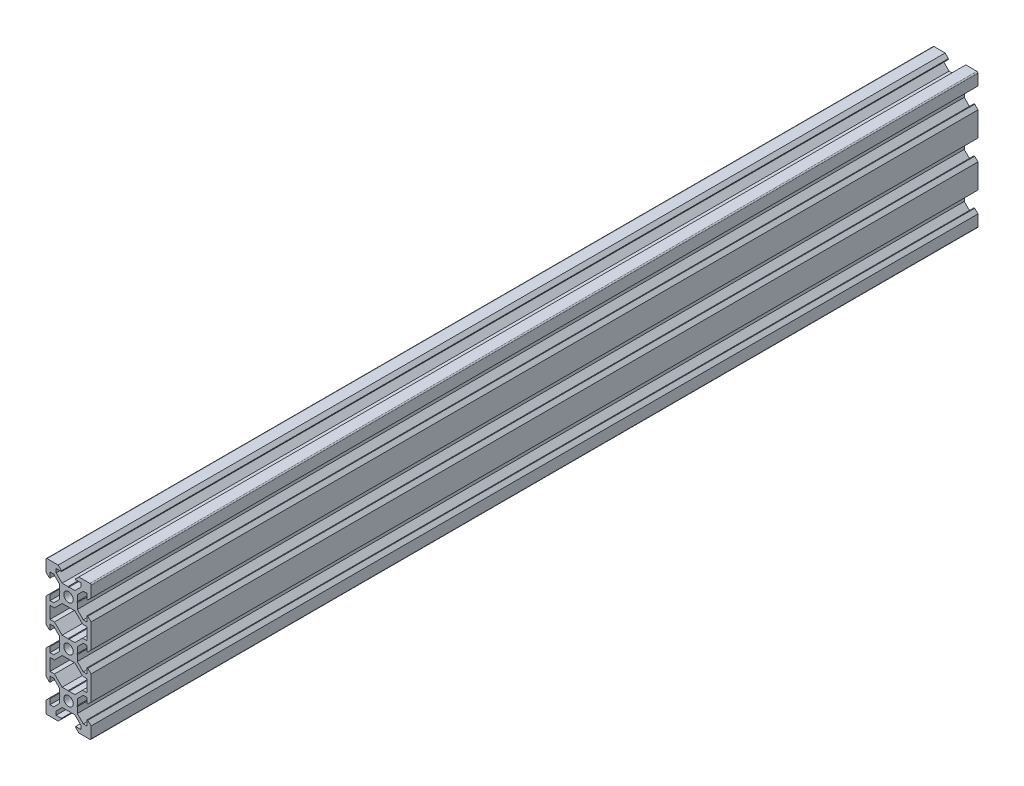
SolidWorks part; units mm, degrees
ref_plane "Plan de face" through (0, 0, 0) normal (0, 0, 1) x (1, 0, 0)
ref_plane "Plan de dessus" through (0, 0, 0) normal (0, 1, 0) x (1, 0, 0)
ref_plane "Plan de droite" through (0, 0, 0) normal (1, 0, 0) x (0, 0, -1)
ref_axis "Axe" through (0, 0, -13.782) along (0, 0, 1)
sketch "Esquisse1" plane through (0, 0, 0) normal (0, 0, 1) x (1, 0, 0)
  line L0 (0, 27.6392) -> (0, -27.6392) construction
  line L1 (-33.6074, 0) -> (33.6074, 0) construction
  line L2 (0, 0) -> (-22.2114, 22.2114) construction
  line L3 (-9.5, 10) -> (-4.58, 10)
  line L4 (-4.58, 10) -> (-3.125, 8.545)
  line L5 (-3.125, 8.545) -> (-3.125, 8.2)
  line L6 (-3.125, 8.2) -> (-5.5, 8.2)
  line L7 (-2.8393, 3.9) -> (-5.5, 6.5607)
  line L8 (-2.8393, 3.9) -> (-0.21, 3.9)
  line L9 (-5.5, 6.5607) -> (-5.5, 8.2)
  line L10 (0, 3.69) -> (0, 2.1)
  line L11 (-3.9, 2.8393) -> (-6.5607, 5.5)
  line L12 (-8.545, 3.125) -> (-8.2, 3.125)
  line L13 (-8.2, 3.125) -> (-8.2, 5.5)
  line L14 (-6.5607, 5.5) -> (-8.2, 5.5)
  line L15 (-10, 4.58) -> (-8.545, 3.125)
  line L16 (-10, 9.5) -> (-10, 4.58)
  line L17 (-0.21, 3.9) -> (0, 3.69)
  line L18 (-3.9, 2.8393) -> (-3.9, 0.21)
  line L19 (-6.2393, -12.7) -> (-8.2, -12.7)
  line L20 (-3.9, 0.21) -> (-3.69, 0)
  line L21 (-0.21, -3.9) -> (0, -3.69)
  line L22 (0, -3.69) -> (0, -2.1)
  line L23 (-6.5607, -5.5) -> (-8.2, -5.5)
  line L24 (-2.8393, -3.9) -> (-0.21, -3.9)
  line L25 (-8.545, -3.125) -> (-8.2, -3.125)
  line L26 (-10, -4.58) -> (-8.545, -3.125)
  line L27 (-8.2, -3.125) -> (-8.2, -5.5)
  line L28 (-2.8393, -3.9) -> (-6.2393, -7.3)
  line L29 (-3.9, -2.8393) -> (-6.5607, -5.5)
  line L30 (-3.9, -2.8393) -> (-3.9, -0.21)
  line L31 (-3.9, -0.21) -> (-3.69, 0)
  line L32 (-6.2393, -7.3) -> (-8.2, -7.3)
  line L33 (-8.2, -7.3) -> (-8.2, -12.7)
  line L34 (-8.2, -10) -> (-10, -10) construction
  line L35 (-10, -15.42) -> (-10, -4.58)
  line L36 (-3.9, -19.79) -> (-3.69, -20)
  line L37 (-3.9, -17.1607) -> (-3.9, -19.79)
  line L38 (-3.9, -17.1607) -> (-6.5607, -14.5)
  line L39 (-2.8393, -16.1) -> (-6.2393, -12.7)
  line L40 (-8.2, -16.875) -> (-8.2, -14.5)
  line L41 (-10, -15.42) -> (-8.545, -16.875)
  line L42 (-8.545, -16.875) -> (-8.2, -16.875)
  line L43 (-2.8393, -16.1) -> (-0.21, -16.1)
  line L44 (-6.5607, -14.5) -> (-8.2, -14.5)
  line L45 (0, -16.31) -> (0, -17.9)
  line L46 (-0.21, -16.1) -> (0, -16.31)
  line L47 (-8.2, -30) -> (-10, -30) construction
  line L48 (-3.69, -20) -> (0, -20) construction
  line L49 (-0.21, -23.9) -> (0, -23.69)
  line L50 (0, -23.69) -> (0, -22.1)
  line L51 (-6.5607, -25.5) -> (-8.2, -25.5)
  line L52 (-2.8393, -23.9) -> (-0.21, -23.9)
  line L53 (-8.545, -23.125) -> (-8.2, -23.125)
  line L54 (-10, -24.58) -> (-8.545, -23.125)
  line L55 (-8.2, -23.125) -> (-8.2, -25.5)
  line L56 (-2.8393, -23.9) -> (-6.2393, -27.3)
  line L57 (-3.9, -22.8393) -> (-6.5607, -25.5)
  line L58 (-3.9, -22.8393) -> (-3.9, -20.21)
  line L59 (-3.9, -20.21) -> (-3.69, -20)
  line L60 (-10, -24.58) -> (-10, -35.42)
  line L61 (-8.2, -32.7) -> (-8.2, -27.3)
  line L62 (-6.2393, -32.7) -> (-8.2, -32.7)
  line L63 (-3.9, -39.79) -> (-3.69, -40)
  line L64 (-3.9, -37.1607) -> (-3.9, -39.79)
  line L65 (-3.9, -37.1607) -> (-6.5607, -34.5)
  line L66 (-2.8393, -36.1) -> (-6.2393, -32.7)
  line L67 (-8.2, -36.875) -> (-8.2, -34.5)
  line L68 (-10, -35.42) -> (-8.545, -36.875)
  line L69 (-8.545, -36.875) -> (-8.2, -36.875)
  line L70 (-2.8393, -36.1) -> (-0.21, -36.1)
  line L71 (-6.5607, -34.5) -> (-8.2, -34.5)
  line L72 (0, -36.31) -> (0, -37.9)
  line L73 (-0.21, -36.1) -> (0, -36.31)
  line L74 (-3.9, -40.21) -> (-3.69, -40)
  line L75 (-6.2393, -27.3) -> (-8.2, -27.3)
  line L76 (-3.9, -42.8393) -> (-3.9, -40.21)
  line L77 (-0.21, -43.9) -> (0, -43.69)
  line L78 (-10, -49.5) -> (-10, -44.58)
  line L79 (-10, -44.58) -> (-8.545, -43.125)
  line L80 (-6.5607, -45.5) -> (-8.2, -45.5)
  line L81 (-8.2, -43.125) -> (-8.2, -45.5)
  line L82 (-8.545, -43.125) -> (-8.2, -43.125)
  line L83 (-3.9, -42.8393) -> (-6.5607, -45.5)
  line L84 (0, -43.69) -> (0, -42.1)
  line L85 (-5.5, -46.5607) -> (-5.5, -48.2)
  line L86 (-2.8393, -43.9) -> (-0.21, -43.9)
  line L87 (-2.8393, -43.9) -> (-5.5, -46.5607)
  line L88 (-3.125, -48.2) -> (-5.5, -48.2)
  line L89 (-3.125, -48.545) -> (-3.125, -48.2)
  line L90 (-4.58, -50) -> (-3.125, -48.545)
  line L91 (-9.5, -50) -> (-4.58, -50)
  arc A0 (0, -2.1) -> (0, 2.1) centre (0, 0) cw
  arc A1 (-9.5, 10) -> (-10, 9.5) centre (-9.5, 9.5) ccw
  arc A2 (0, -37.9) -> (0, -42.1) centre (0, -40) ccw
  arc A3 (-9.5, -50) -> (-10, -49.5) centre (-9.5, -49.5) cw
  arc A4 (0, -17.9) -> (0, -22.1) centre (0, -20) ccw
  point P4 (0, 0)
  point P7 (0, 0)
  point P30 (-10, 10)
  point P60 (0, -20)
  point P111 (-10, -50)
  dimension "D5" = 11
  dimension "D2" = 2.1
  dimension "D3" = 6.25
  dimension "D10" = 0.5
  dimension "D4" = 9.16
  dimension "D6" = 1.5
  dimension "D7" = 1.8
  dimension "D8" = 4.3
  dimension "D9" = 20
  dimension "D11" = 0.42
  dimension "D12" = 10
  dimension "D13" = 1.8
extrude "Boss.-Extru.1" add sketch "Esquisse1" along normal blind 393.7
sketch "Esquisse3" plane through (0, 0, 393.7) normal (0, 0, 1) x (1, 0, 0)
  line L0 (0, 0) -> (-9.8536, 9.8536) construction
  line L1 (-8.2, 8.2) -> (-8.2, 6.57)
  line L2 (-8.2, 6.57) -> (-7.54, 6.57)
  line L3 (-7.54, 6.57) -> (-6.57, 7.54)
  line L4 (-8.2, 3.125) -> (-8.2, 5.5) construction
  line L5 (-6.57, 8.2) -> (-6.57, 7.54)
  line L6 (-8.2, 8.2) -> (-6.57, 8.2)
  line L7 (-5.5, 6.5607) -> (-5.5, 8.2) construction
  line L8 (-3.69, -20) -> (0, -20) construction
  line L9 (-8.2, -48.2) -> (-6.57, -48.2)
  line L10 (-6.57, -48.2) -> (-6.57, -47.54)
  line L11 (-7.54, -46.57) -> (-6.57, -47.54)
  line L12 (-8.2, -46.57) -> (-7.54, -46.57)
  line L13 (-8.2, -48.2) -> (-8.2, -46.57)
  arc A0 (-9.5, 10) -> (-10, 9.5) centre (-9.5, 9.5) ccw construction
  point P13 (-7.055, 7.055)
  point P14 (-6.57, 7.87)
  point P26 (-7.055, -47.055)
  dimension "D1" = 1.07
extrude "Enlèv. mat.-Extru.1" [suppressed] cut sketch "Esquisse3" against normal through all
mirror "Symétrie1" about plane through (0, 3.69, 393.7) normal (-1, 0, 0) of "Enlèv. mat.-Extru.1", "Boss.-Extru.1"
